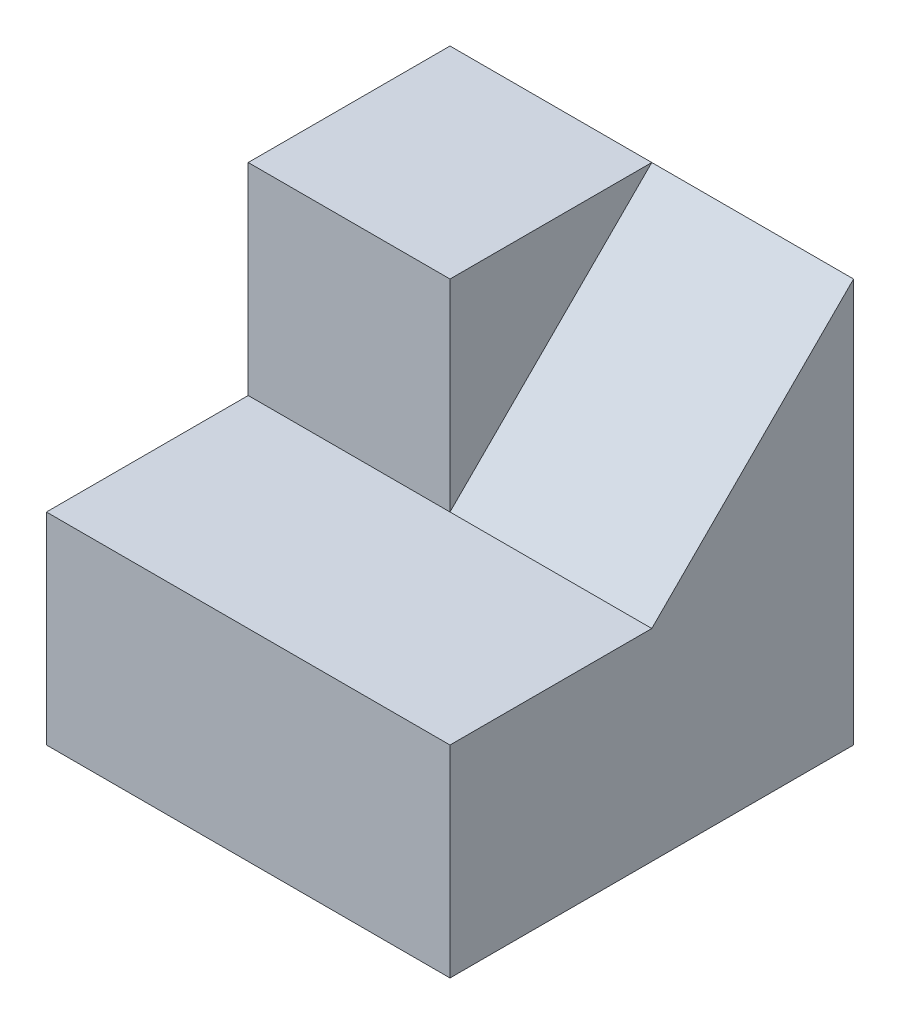
SolidWorks part; units mm, degrees
ref_plane "Alzado" through (0, 0, 0) normal (0, 0, 1) x (1, 0, 0)
ref_plane "Planta" through (0, 0, 0) normal (0, 1, 0) x (1, 0, 0)
ref_plane "Vista lateral" through (0, 0, 0) normal (1, 0, 0) x (0, 0, -1)
sketch "Croquis1" plane through (0, 0, 0) normal (0, 1, 0) x (1, 0, 0)
  line L1 (-40.4285, 72.7378) -> (59.5715, 72.7378)
  line L2 (-40.4285, 72.7378) -> (-40.4285, -27.2622)
  line L3 (-40.4285, -27.2622) -> (59.5715, -27.2622)
  line L4 (59.5715, 72.7378) -> (59.5715, -27.2622)
  dimension "D1" = 100
  dimension "D2" = 100
extrude "Saliente-Extruir1" add sketch "Croquis1" along normal blind 50
sketch "Croquis2" plane through (0, 50, 0) normal (0, 1, 0) x (1, 0, 0)
  line L1 (-40.4285, 72.7378) -> (9.5715, 72.7378)
  line L2 (-40.4285, 72.7378) -> (-40.4285, 22.7378)
  line L3 (-40.4285, 22.7378) -> (9.5715, 22.7378)
  line L4 (9.5715, 72.7378) -> (9.5715, 22.7378)
  dimension "D1" = 50
  dimension "D2" = 50
extrude "Saliente-Extruir3" add sketch "Croquis2" along normal blind 50
sketch "Croquis3" plane through (59.5715, 0, 0) normal (1, 0, 0) x (0, 0, -1)
  line L0 (22.7378, 50) -> (72.7378, 100)
  line L1 (-27.2622, 50) -> (72.7378, 50) construction
  line L2 (72.7378, 100) -> (72.7378, 50) construction
  line L3 (72.7378, 100) -> (72.7378, 50)
  line L4 (72.7378, 50) -> (22.7378, 50)
extrude "Saliente-Extruir4" add sketch "Croquis3" against normal blind 50
